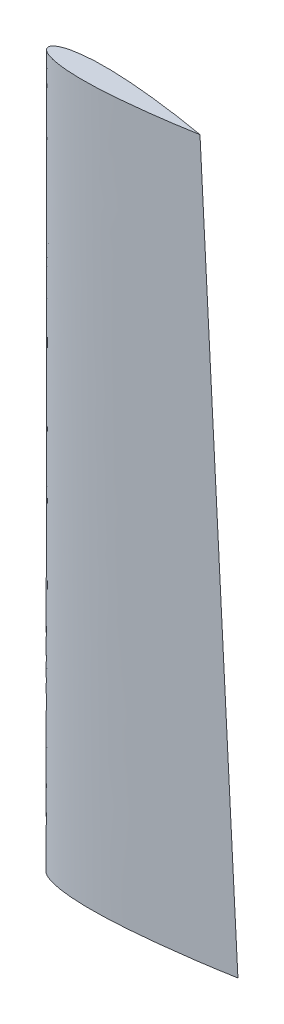
SolidWorks part; units mm, degrees
ref_plane "Front Plane" through (0, 0, 0) normal (0, 0, 1) x (1, 0, 0)
ref_plane "Top Plane" through (0, 0, 0) normal (0, 1, 0) x (1, 0, 0)
ref_plane "Right Plane" through (0, 0, 0) normal (1, 0, 0) x (0, 0, -1)
sketch "rootSketch" plane through (0, 0, 0) normal (0, 1, 0) x (1, 0, 0)
  line L0 (0, 0) -> (1500, 0) construction
  line L2 (130, -39) -> (130, 39) construction
  line L3 (0, 0) -> (520, 0) construction
  spline S0 degree 4 poles (0, 0) (-0.0001, 0.5654) (0.0536, 1.4802) (0.2607, 2.8027) (0.7777, 4.522) (1.4706, 6.1188) (2.4853, 7.8597) (3.9236, 9.7755) (5.9919, 11.9542) (9.0582, 14.5182) (13.7048, 17.5792) (20.7825, 21.1911) (31.7576, 25.4204) (48.232, 29.987) (72.7551, 34.5297) (104.3849, 37.8048) (136.2818, 39.0905) (166.3809, 39.0862) (196.4662, 38.3106) (221.5182, 37.1099) (246.5436, 35.4647) (271.5411, 33.4472) (291.522, 31.6348) (311.4856, 29.6435) (331.4329, 27.4893) (348.8708, 25.4726) (363.8089, 23.6551) (376.2472, 22.0838) (386.1986, 20.7921) (398.6215, 19.1378) (413.5397, 17.0827) (430.8967, 14.595) (450.7686, 11.6077) (468.0611, 8.8865) (482.9855, 6.442) (495.2251, 4.3757) (504.1169, 2.835) (511.0796, 1.6079) (518.469, 0.2799) (522.2276, -0.4041) (527.6198, -1.3949) (532.051, -2.2221) (537.2004, -3.1898) (542.7114, -4.2436) (549.3261, -5.5266) (555.7484, -6.7962) (561.4804, -7.9471) (565.909, -8.8508) (569.1689, -9.5219) (570.7832, -9.8566) (571.594, -10.0251) (571.9999, -10.1096) knots 0 0 0 0 0 0.003841 0.006235 0.009072 0.012193 0.015657 0.019917 0.025339 0.032593 0.042799 0.057705 0.079311 0.112503 0.158973 0.227236 0.2955 0.329632 0.363764 0.432028 0.46616 0.500292 0.534424 0.568556 0.602688 0.63682 0.653886 0.670952 0.688018 0.705084 0.739215 0.773347 0.807479 0.841611 0.858677 0.875743 0.892809 0.901342 0.909875 0.921141 0.926774 0.932406 0.943672 0.954938 0.966203 0.977469 0.988734 0.994367 0.997184 1 1 1 1 1 construction
  spline S1 degree 4 poles (0, 0) (-0.0001, 0.5654) (0.0536, 1.4802) (0.2607, 2.8027) (0.7777, 4.522) (1.4706, 6.1188) (2.4853, 7.8597) (3.9236, 9.7755) (5.9919, 11.9542) (9.0582, 14.5182) (13.7048, 17.5792) (20.7825, 21.1911) (31.7576, 25.4204) (48.232, 29.987) (72.7551, 34.5297) (104.3849, 37.8048) (136.2818, 39.0905) (166.3809, 39.0862) (196.4662, 38.3106) (221.5182, 37.1099) (246.5436, 35.4647) (271.5411, 33.4472) (291.522, 31.6348) (311.4856, 29.6435) (331.4329, 27.4893) (348.8708, 25.4726) (363.8089, 23.6551) (376.2472, 22.0838) (386.1986, 20.7921) (398.6215, 19.1378) (413.5397, 17.0827) (430.8967, 14.595) (450.7686, 11.6077) (468.0611, 8.8865) (482.9855, 6.442) (495.2251, 4.3757) (504.1169, 2.835) (511.0796, 1.6079) (516.6353, 0.6095) (518.8775, 0.2039) (520, 0) knots 0 0 0 0 0 0.003841 0.006235 0.009072 0.012193 0.015657 0.019917 0.025339 0.032593 0.042799 0.057705 0.079311 0.112503 0.158973 0.227236 0.2955 0.329632 0.363764 0.432028 0.46616 0.500292 0.534424 0.568556 0.602688 0.63682 0.653886 0.670952 0.688018 0.705084 0.739215 0.773347 0.807479 0.841611 0.858677 0.875743 0.892809 0.901342 0.909875 0.909875 0.909875 0.909875 0.909875
  spline S2 degree 4 poles (0, 0) (-0.0001, -0.5654) (0.0536, -1.4802) (0.2607, -2.8027) (0.7777, -4.522) (1.4706, -6.1188) (2.4853, -7.8597) (3.9236, -9.7755) (5.9919, -11.9542) (9.0582, -14.5182) (13.7048, -17.5792) (20.7825, -21.1911) (31.7576, -25.4204) (48.232, -29.987) (72.7551, -34.5297) (104.3849, -37.8048) (136.2818, -39.0905) (166.3809, -39.0862) (196.4662, -38.3106) (221.5182, -37.1099) (246.5436, -35.4647) (271.5411, -33.4472) (291.522, -31.6348) (311.4856, -29.6435) (331.4329, -27.4893) (348.8708, -25.4726) (363.8089, -23.6551) (376.2472, -22.0838) (386.1986, -20.7921) (398.6215, -19.1378) (413.5397, -17.0827) (430.8967, -14.595) (450.7686, -11.6077) (468.0611, -8.8865) (482.9855, -6.442) (495.2251, -4.3757) (504.1169, -2.835) (511.0796, -1.6079) (518.469, -0.2799) (522.2276, 0.4041) (527.6198, 1.3949) (532.051, 2.2221) (537.2004, 3.1898) (542.7114, 4.2436) (549.3261, 5.5266) (555.7484, 6.7962) (561.4804, 7.9471) (565.909, 8.8508) (569.1689, 9.5219) (570.7832, 9.8566) (571.594, 10.0251) (571.9999, 10.1096) knots 0 0 0 0 0 0.003841 0.006235 0.009072 0.012193 0.015657 0.019917 0.025339 0.032593 0.042799 0.057705 0.079311 0.112503 0.158973 0.227236 0.2955 0.329632 0.363764 0.432028 0.46616 0.500292 0.534424 0.568556 0.602688 0.63682 0.653886 0.670952 0.688018 0.705084 0.739215 0.773347 0.807479 0.841611 0.858677 0.875743 0.892809 0.901342 0.909875 0.921141 0.926774 0.932406 0.943672 0.954938 0.966203 0.977469 0.988734 0.994367 0.997184 1 1 1 1 1 construction
  spline S3 degree 4 poles (0, 0) (-0.0001, -0.5654) (0.0536, -1.4802) (0.2607, -2.8027) (0.7777, -4.522) (1.4706, -6.1188) (2.4853, -7.8597) (3.9236, -9.7755) (5.9919, -11.9542) (9.0582, -14.5182) (13.7048, -17.5792) (20.7825, -21.1911) (31.7576, -25.4204) (48.232, -29.987) (72.7551, -34.5297) (104.3849, -37.8048) (136.2818, -39.0905) (166.3809, -39.0862) (196.4662, -38.3106) (221.5182, -37.1099) (246.5436, -35.4647) (271.5411, -33.4472) (291.522, -31.6348) (311.4856, -29.6435) (331.4329, -27.4893) (348.8708, -25.4726) (363.8089, -23.6551) (376.2472, -22.0838) (386.1986, -20.7921) (398.6215, -19.1378) (413.5397, -17.0827) (430.8967, -14.595) (450.7686, -11.6077) (468.0611, -8.8865) (482.9855, -6.442) (495.2251, -4.3757) (504.1169, -2.835) (511.0796, -1.6079) (516.6353, -0.6095) (518.8775, -0.2039) (520, 0) knots 0 0 0 0 0 0.003841 0.006235 0.009072 0.012193 0.015657 0.019917 0.025339 0.032593 0.042799 0.057705 0.079311 0.112503 0.158973 0.227236 0.2955 0.329632 0.363764 0.432028 0.46616 0.500292 0.534424 0.568556 0.602688 0.63682 0.653886 0.670952 0.688018 0.705084 0.739215 0.773347 0.807479 0.841611 0.858677 0.875743 0.892809 0.901342 0.909875 0.909875 0.909875 0.909875 0.909875
  point P10 (130, 0)
  dimension "incidenceAngle" = 0
  dimension "rootChord" = 520
  dimension "rootQuarterChord" = 130
  dimension "rootMaxThickness" = 78
ref_plane "Plane1" through (0, 1950.0156, 0) normal (0, 1, 0) x (1, 0, 0)
sketch "tipSketch" plane through (0, 1950.0156, 0) normal (0, 1, 0) x (1, 0, 0)
  line L0 (216.8234, 0) -> (518.1352, 0) construction
  line L3 (0, 0) -> (416, 0) construction
  line L4 (104, -31.2) -> (104, 31.2) construction
  spline S0 degree 4 poles (0, 0) (-0.0001, 0.4526) (0.0429, 1.1842) (0.2086, 2.2419) (0.6222, 3.6177) (1.1765, 4.895) (1.9882, 6.2878) (3.1389, 7.8203) (4.7935, 9.5634) (7.2466, 11.6145) (10.9638, 14.0633) (16.626, 16.9529) (25.4061, 20.3363) (38.5856, 23.9896) (58.2041, 27.6238) (83.5079, 30.2438) (109.0255, 31.2724) (133.1047, 31.269) (157.1729, 30.6485) (177.2146, 29.6879) (197.2349, 28.3717) (217.2329, 26.7577) (233.2176, 25.3079) (249.1886, 23.7148) (265.1461, 21.9915) (279.097, 20.378) (291.0466, 18.9242) (300.9987, 17.6669) (308.9572, 16.634) (318.9003, 15.3097) (330.8261, 13.6672) (344.7266, 11.6743) (360.6007, 9.2888) (374.4705, 7.1053) (386.3552, 5.1597) (395.2488, 3.6571) (400.7019, 2.7171) (404.6252, 2.0315) (407.6573, 1.4968) (410.4147, 1.0078) (414.7874, 0.2217) (418.3137, -0.42) (424.2238, -1.5084) (428.7757, -2.367) (434.3776, -3.4328) (439.3296, -4.3974) (444.6898, -5.4535) (449.7621, -6.4751) (453.7451, -7.2876) (456.2875, -7.8149) (457.6029, -8.0882) knots 0 0 0 0 0 0.003841 0.006235 0.009072 0.012193 0.015657 0.019917 0.025339 0.032593 0.042799 0.057705 0.079311 0.112503 0.158973 0.227236 0.2955 0.329632 0.363764 0.432028 0.46616 0.500292 0.534424 0.568556 0.602688 0.63682 0.653886 0.670952 0.688018 0.705084 0.739215 0.773347 0.807479 0.841611 0.858677 0.875743 0.884276 0.888543 0.892809 0.901342 0.909875 0.921141 0.932406 0.943672 0.954938 0.966203 0.977469 0.988734 1 1 1 1 1 construction
  spline S1 degree 4 poles (0, 0) (-0.0001, 0.4526) (0.0429, 1.1842) (0.2086, 2.2419) (0.6222, 3.6177) (1.1765, 4.895) (1.9882, 6.2878) (3.1389, 7.8203) (4.7935, 9.5634) (7.2466, 11.6145) (10.9638, 14.0633) (16.626, 16.9529) (25.4061, 20.3363) (38.5856, 23.9896) (58.2041, 27.6238) (83.5079, 30.2438) (109.0255, 31.2724) (133.1047, 31.269) (157.1729, 30.6485) (177.2146, 29.6879) (197.2349, 28.3717) (217.2329, 26.7577) (233.2176, 25.3079) (249.1886, 23.7148) (265.1461, 21.9915) (279.097, 20.378) (291.0466, 18.9242) (300.9987, 17.6669) (308.9572, 16.634) (318.9003, 15.3097) (330.8261, 13.6672) (344.7266, 11.6743) (360.6007, 9.2888) (374.4705, 7.1053) (386.3552, 5.1597) (395.2488, 3.6571) (400.7019, 2.7171) (404.6252, 2.0315) (407.6573, 1.4968) (410.4147, 1.0078) (413.2762, 0.4934) (415.102, 0.1632) (416, 0) knots 0 0 0 0 0 0.003841 0.006235 0.009072 0.012193 0.015657 0.019917 0.025339 0.032593 0.042799 0.057705 0.079311 0.112503 0.158973 0.227236 0.2955 0.329632 0.363764 0.432028 0.46616 0.500292 0.534424 0.568556 0.602688 0.63682 0.653886 0.670952 0.688018 0.705084 0.739215 0.773347 0.807479 0.841611 0.858677 0.875743 0.884276 0.888543 0.892809 0.901342 0.909875 0.909875 0.909875 0.909875 0.909875
  spline S2 degree 4 poles (0, 0) (-0.0001, -0.4526) (0.0429, -1.1842) (0.2086, -2.2419) (0.6222, -3.6177) (1.1765, -4.895) (1.9882, -6.2878) (3.1389, -7.8203) (4.7935, -9.5634) (7.2466, -11.6145) (10.9638, -14.0633) (16.626, -16.9529) (25.4061, -20.3363) (38.5856, -23.9896) (58.2041, -27.6238) (83.5079, -30.2438) (109.0255, -31.2724) (133.1047, -31.269) (157.1729, -30.6485) (177.2146, -29.6879) (197.2349, -28.3717) (217.2329, -26.7577) (233.2176, -25.3079) (249.1886, -23.7148) (265.1461, -21.9915) (279.097, -20.378) (291.0466, -18.9242) (300.9987, -17.6669) (308.9572, -16.634) (318.9003, -15.3097) (330.8261, -13.6672) (344.7266, -11.6743) (360.6007, -9.2888) (374.4705, -7.1053) (386.3552, -5.1597) (395.2488, -3.6571) (400.7019, -2.7171) (404.6252, -2.0315) (407.6573, -1.4968) (410.4147, -1.0078) (414.7874, -0.2217) (418.3137, 0.42) (424.2238, 1.5084) (428.7757, 2.367) (434.3776, 3.4328) (439.3296, 4.3974) (444.6898, 5.4535) (449.7621, 6.4751) (453.7451, 7.2876) (456.2875, 7.8149) (457.6029, 8.0882) knots 0 0 0 0 0 0.003841 0.006235 0.009072 0.012193 0.015657 0.019917 0.025339 0.032593 0.042799 0.057705 0.079311 0.112503 0.158973 0.227236 0.2955 0.329632 0.363764 0.432028 0.46616 0.500292 0.534424 0.568556 0.602688 0.63682 0.653886 0.670952 0.688018 0.705084 0.739215 0.773347 0.807479 0.841611 0.858677 0.875743 0.884276 0.888543 0.892809 0.901342 0.909875 0.921141 0.932406 0.943672 0.954938 0.966203 0.977469 0.988734 1 1 1 1 1 construction
  spline S3 degree 4 poles (0, 0) (-0.0001, -0.4526) (0.0429, -1.1842) (0.2086, -2.2419) (0.6222, -3.6177) (1.1765, -4.895) (1.9882, -6.2878) (3.1389, -7.8203) (4.7935, -9.5634) (7.2466, -11.6145) (10.9638, -14.0633) (16.626, -16.9529) (25.4061, -20.3363) (38.5856, -23.9896) (58.2041, -27.6238) (83.5079, -30.2438) (109.0255, -31.2724) (133.1047, -31.269) (157.1729, -30.6485) (177.2146, -29.6879) (197.2349, -28.3717) (217.2329, -26.7577) (233.2176, -25.3079) (249.1886, -23.7148) (265.1461, -21.9915) (279.097, -20.378) (291.0466, -18.9242) (300.9987, -17.6669) (308.9572, -16.634) (318.9003, -15.3097) (330.8261, -13.6672) (344.7266, -11.6743) (360.6007, -9.2888) (374.4705, -7.1053) (386.3552, -5.1597) (395.2488, -3.6571) (400.7019, -2.7171) (404.6252, -2.0315) (407.6573, -1.4968) (410.4147, -1.0078) (413.2762, -0.4934) (415.102, -0.1632) (416, 0) knots 0 0 0 0 0 0.003841 0.006235 0.009072 0.012193 0.015657 0.019917 0.025339 0.032593 0.042799 0.057705 0.079311 0.112503 0.158973 0.227236 0.2955 0.329632 0.363764 0.432028 0.46616 0.500292 0.534424 0.568556 0.602688 0.63682 0.653886 0.670952 0.688018 0.705084 0.739215 0.773347 0.807479 0.841611 0.858677 0.875743 0.884276 0.888543 0.892809 0.901342 0.909875 0.909875 0.909875 0.909875 0.909875
  point P10 (104, 0)
  dimension "incidenceAngle" = 0
  dimension "tipChord" = 416
  dimension "tipQuarterChord" = 104
  dimension "tipMaxThickness" = 62.4
  dimension "sweepOffset" = 0
  dimension "D1" = 0
  dimension "D2" = 0
loft "Loft1" add profiles "rootSketch", "tipSketch" connector at (0, 0, 0) connector at (0, 1950.0156, 0)
ref_plane "Plane2" through (520, 0, 0) normal (1, 0, 0) x (0, 0, -1)
sketch "rudderSketch" plane through (0, 0, 0) normal (0, 0, 1) x (1, 0, 0)
  line L0 (0, 0) -> (0, 487.5039) construction
  line L1 (0, 0) -> (0, 1462.5117) construction
  line L2 (0, 487.5039) -> (247, 487.5039) construction
  line L3 (0, 1462.5117) -> (247, 1462.5117) construction
  line L4 (247, 1462.5117) -> (247, 487.5039)
  line L5 (247, 1462.5117) -> (767, 1462.5117)
  line L6 (247, 487.5039) -> (767, 487.5039)
  line L7 (767, 487.5039) -> (767, 1462.5117)
  line L8 (763.1, 491.4039) -> (763.1, 1458.6117)
  line L9 (250.9, 1458.6117) -> (763.1, 1458.6117)
  line L10 (250.9, 1458.6117) -> (250.9, 491.4039)
  line L11 (250.9, 491.4039) -> (763.1, 491.4039)
  dimension "rudderStartyLoc" = 487.5039
  dimension "rudderEndyLoc" = 1462.5117
  dimension "rudderStartxLoc" = 247
  dimension "rudderEndeLoc" = 247
  dimension "D1" = 520
  dimension "D2" = 520
  dimension "D3" = 3.9
extrude "Cut-Extrude1" [suppressed] cut sketch "rudderSketch" against normal blind 200 and the other way blind 200
equation "\"rootChord@rootSketch\"=(\"rootChord\"+\"rootChord\")/2"
equation "\"incidenceAngle@rootSketch\"=(\"incidentAngle\"+\"incidentAngle\")/2"
equation "\"rootQuarterChord@rootSketch\" = \"rootChord@rootSketch\" / 4"
equation "\"rootMaxThickness@rootSketch\" = \"rootChord\" * \"NACAairfoil\" / 100"
equation "\"halfSpan@Plane1\"= \"rootChord@rootSketch\" * ( 1 + \"taperRatio\" ) / 2 * \"aspectRatio\""
equation "\"incidenceAngle@tipSketch\" = \"incidenceAngle@rootSketch\""
equation "\"tipChord@tipSketch\"= \"rootChord@rootSketch\" * \"taperRatio\""
equation "\"tipQuarterChord@tipSketch\"=\"tipChord@tipSketch\"/4"
equation "\"tipMaxThickness@tipSketch\"=\"tipChord@tipSketch\"*\"NACAairfoil\"/100"
equation "\"rootChord@Plane2\"=\"rootChord@rootSketch\""
equation "\"rudderCenter\"= 0.5'Center of the rudder as a percentage of half span"
equation "\"rudderWidth\"= 0.5'Width of the rudder as a percentage of half span"
equation "\"rudderStartyLoc@rudderSketch\"=\"halfSpan@Plane1\" *  ( \"rudderCenter\" - \"rudderWidth\" / 2 )"
equation "\"rudderEndyLoc@rudderSketch\"=\"halfSpan@Plane1\" *  ( \"rudderCenter\" + \"rudderWidth\" / 2 )"
equation "\"rudderStartxLoc@rudderSketch\"=\"rudderStartyLoc@rudderSketch\"*tan ( \"sweepAngle\" ) + 0.5*(\"rootChord@rootSketch\" + \"rudderStartyLoc@rudderSketch\"*(((\"tipChord@tipSketch\"-\"rootChord@rootSketch\")/\"halfSpan@Plane1\")))"
equation "\"rudderEndeLoc@rudderSketch\"=\"rudderStartyLoc@rudderSketch\"*tan ( \"sweepAngle\" ) + 0.5*(\"rootChord@rootSketch\" + \"rudderStartyLoc@rudderSketch\"*(((\"tipChord@tipSketch\"-\"rootChord@rootSketch\")/\"halfSpan@Plane1\")))"
equation "\"D1@rudderSketch\"=1*\"rootChord@rootSketch\""
equation "\"D2@rudderSketch\"=1*\"rootChord@rootSketch\""
equation "\"D3@rudderSketch\"=\"halfSpan@Plane1\"/500"
equation "\"sweepOffset@tipSketch\" = \"halfSpan@Plane1\" * tan ( \"sweepAngle\" ) "
equation "\"D2@tipSketch\"=\"tipChord@tipSketch\"*tan(\"incidentAngle\")"
equation "\"rootChord\"= 0.52"
equation "\"NACAairfoil\"= 0015"
equation "\"incidentAngle\"= 0"
equation "\"aspectRatio\"= 4.1667"
equation "\"taperRatio\"= 0.8"
equation "\"sweepAngle\"= 0"
